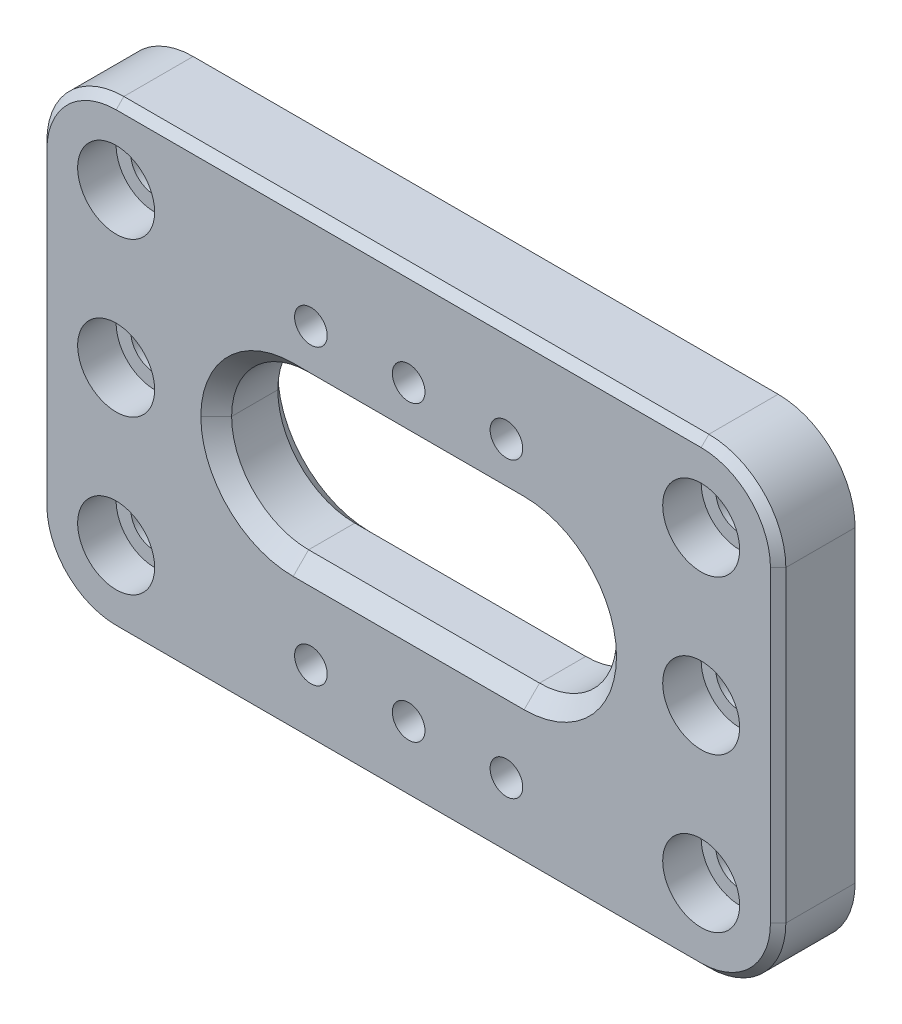
SolidWorks part; units mm, degrees
ref_plane "前视基准面" through (0, 0, 0) normal (0, 0, 1) x (1, 0, 0)
ref_plane "上视基准面" through (0, 0, 0) normal (0, 1, 0) x (1, 0, 0)
ref_plane "右视基准面" through (0, 0, 0) normal (1, 0, 0) x (0, 0, -1)
sketch "草图1" plane through (0, 0, 0) normal (0, 0, 1) x (1, 0, 0)
  line L1 (-48, 30) -> (48, 30)
  line L2 (-48, 30) -> (-48, -30)
  line L3 (-48, -30) -> (48, -30)
  line L4 (48, 30) -> (48, -30)
  line L5 (-48, 30) -> (48, -30) construction
  line L6 (-48, -30) -> (48, 30) construction
  point P0 (0, 0)
extrude "凸台-拉伸1" add sketch "草图1" along normal blind 10
fillet "圆角1" radius 10 4 edges at (48, -30, 5) (-48, -30, 5) (48, 30, 5) (-48, 30, 5)
sketch "草图2" plane through (0, 0, 10) normal (0, 0, 1) x (1, 0, 0)
  line L0 (0, 30) -> (0, 17.3) construction
  line L1 (38, 30) -> (-38, 30) construction
  line L2 (0, 17.3) -> (-12.7, 17.3) construction
  line L3 (0, 17.3) -> (0, -20.8) construction
  line L4 (0, -20.8) -> (-12.7, -20.8) construction
  line L5 (0, -20.8) -> (12.7, -20.8) construction
  circle A0 centre (0, 17.3) radius 2.12
  circle A1 centre (-12.7, 17.3) radius 2.12
  circle A2 centre (12.7, 17.3) radius 2.12
  circle A3 centre (-12.7, -20.8) radius 2.12
  circle A4 centre (0, -20.8) radius 2.12
  circle A5 centre (12.7, -20.8) radius 2.12
  dimension "D1" = 12.7
extrude "切除-拉伸1" cut sketch "草图2" against normal blind 10
sketch "草图3" plane through (0, 0, 10) normal (0, 0, 1) x (1, 0, 0)
  line L0 (-48, 0) -> (-38, 0) construction
  line L1 (-48, 20) -> (-48, -20) construction
  line L2 (-38, 0) -> (-38, 20) construction
  line L3 (-38, 0) -> (-38, -20) construction
  line L4 (0, 0) -> (0, 10) construction
  circle A0 centre (-38, 20) radius 5
  circle A1 centre (-38, 0) radius 5
  circle A2 centre (-38, -20) radius 5
  circle A3 centre (38, -20) radius 5
  circle A4 centre (38, 0) radius 5
  circle A5 centre (38, 20) radius 5
extrude "切除-拉伸2" cut sketch "草图3" against normal blind 5
sketch "草图4" plane through (0, 0, 5) normal (0, 0, 1) x (1, 0, 0)
  circle A0 centre (-38, 20) radius 3.1
  circle A1 centre (-38, 0) radius 3.1
  circle A2 centre (-38, -20) radius 3.1
  circle A3 centre (38, 20) radius 3.1
  circle A4 centre (38, 0) radius 3.1
  circle A5 centre (38, -20) radius 3.1
extrude "切除-拉伸3" cut sketch "草图4" against normal blind 5
chamfer "倒角1" distance 1 angle 45 6 edges at (41.1, 20, 0) (41.1, 0, 0) (41.1, -20, 0) (-34.9, -20, 0) (-34.9, 0, 0) (-34.9, 20, 0)
chamfer "倒角2" distance 1 angle 45 8 edges at (48, 0, 10) (45.0711, 27.0711, 10) (45.0711, -27.0711, 10) (0, 30, 10) (0, -30, 10) (-45.0711, 27.0711, 10) (-45.0711, -27.0711, 10) (-48, 0, 10)
sketch "草图5" plane through (0, 0, 10) normal (0, 0, 1) x (1, 0, 0)
  line L1 (-25, -10) -> (25, -10)
  line L2 (-25, -10) -> (-25, 10)
  line L3 (-25, 10) -> (25, 10)
  line L4 (25, -10) -> (25, 10)
  line L5 (-25, -10) -> (25, 10) construction
  line L6 (-25, 10) -> (25, -10) construction
  point P0 (0, 0)
extrude "切除-拉伸4" cut sketch "草图5" against normal blind 10
fillet "圆角2" radius 10 4 edges at (25, -10, 5) (25, 10, 5) (-25, -10, 5) (-25, 10, 5)
chamfer "倒角3" distance 2 angle 45 12 edges at (22.0711, -7.0711, 0) (22.0711, 7.0711, 0) (0, -10, 0) (0, 10, 0) (-22.0711, -7.0711, 0) (-22.0711, 7.0711, 0) (22.0711, -7.0711, 10) (0, -10, 10) (22.0711, 7.0711, 10) (-22.0711, -7.0711, 10) (0, 10, 10) (-22.0711, 7.0711, 10)
